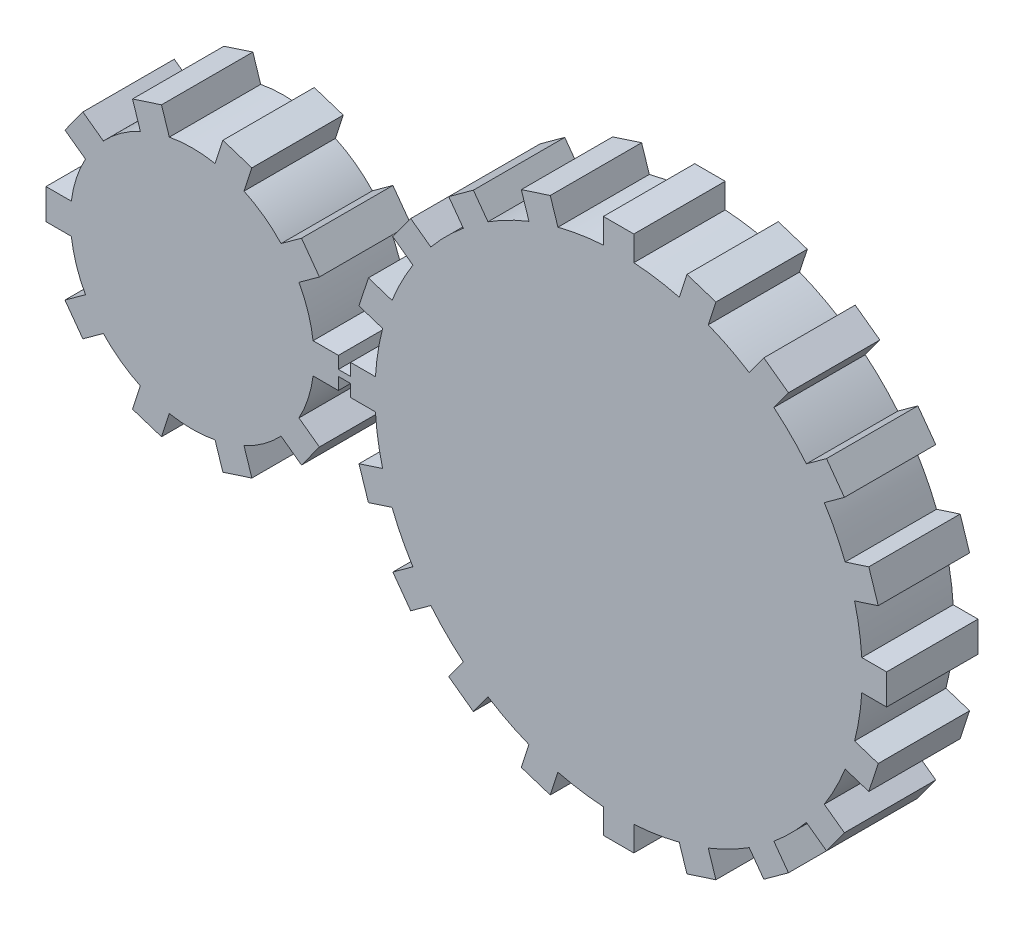
SolidWorks part; units mm, degrees
ref_plane "前视基准面" through (0, 0, 0) normal (0, 0, 1) x (1, 0, 0)
ref_plane "上视基准面" through (0, 0, 0) normal (0, 1, 0) x (1, 0, 0)
ref_plane "右视基准面" through (0, 0, 0) normal (1, 0, 0) x (0, 0, -1)
ref_plane "基准面1" through (0, 0, -7.5) normal (0, 0, 1) x (1, 0, 0)
sketch "草图2" plane through (0, 0, -7.5) normal (0, 0, 1) x (1, 0, 0)
  circle A0 centre (-35, 0) radius 20
extrude "凸台-拉伸2" add sketch "草图2" along normal blind 15
ref_plane "基准面2" through (0, 0, 7.5) normal (0, 0, 1) x (1, 0, 0)
ref_plane "基准面3" through (0, 0, -0.5) normal (0, 0, 1) x (1, 0, 0)
sketch "草图7" plane through (0, 0, -7.5) normal (0, 0, 1) x (1, 0, 0)
  circle A0 centre (35, 0) radius 40
extrude "凸台-拉伸4" add sketch "草图7" along normal blind 15
sketch "草图9" plane through (0, 0, -7.5) normal (0, 0, 1) x (1, 0, 0)
  line L0 (-16, -2.5) -> (-11, -2.5)
  line L1 (-11, -2.5) -> (-11, 2.5)
  line L2 (-11, 2.5) -> (-16, 2.5)
  line L3 (-16, 2.5) -> (-16, -2.5)
extrude "凸台-拉伸6" add sketch "草图9" along normal blind 15
ref_plane "基准面4" through (-35, 0, 0) normal (1, 0, 0) x (0, 0, -1)
ref_axis "基准轴1" through (-35, 0, 8.25) along (0, 0, -1)
pattern_circular "阵列(圆周)1" count 10 over 360 about axis through (-35, 0, 8.25) along (0, 0, -1) of "凸台-拉伸6"
ref_plane "基准面5" through (35, 0, 0) normal (1, 0, 0) x (0, 0, -1)
ref_axis "基准轴2" through (35, 0, 8.25) along (0, 0, -1)
ref_plane "基准面6" through (0, 0, 0.2) normal (0, 0, 1) x (1, 0, 0)
sketch "草图17" plane through (0, 0, -7.5) normal (0, 0, 1) x (1, 0, 0)
  line L0 (-9, -2.5) -> (-4, -2.5)
  line L1 (-4, -2.5) -> (-4, 2.5)
  line L2 (-4, 2.5) -> (-9, 2.5)
  line L3 (-9, 2.5) -> (-9, -2.5)
extrude "凸台-拉伸9" add sketch "草图17" along normal blind 15
pattern_circular "阵列(圆周)3" count 20 over 360 about axis through (35, 0, 8.25) along (0, 0, -1) of "凸台-拉伸9"
sketch "草图18" plane through (0, 0, -7.5) normal (0, 0, 1) x (1, 0, 0)
  line L0 (-11.5, -0.5) -> (-8.5, -0.5)
  line L1 (-8.5, -0.5) -> (-8.5, 0.5)
  line L2 (-8.5, 0.5) -> (-11.5, 0.5)
  line L3 (-11.5, 0.5) -> (-11.5, -0.5)
extrude "凸台-拉伸10" add sketch "草图18" along normal blind 15
